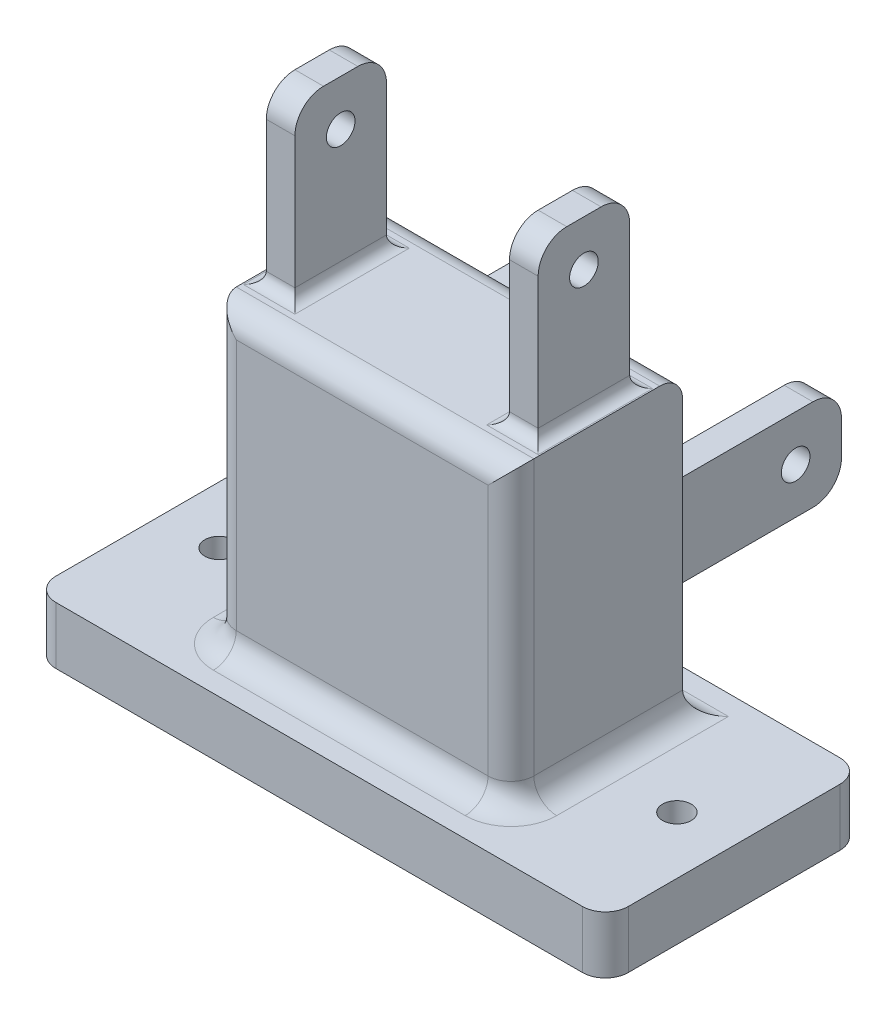
SolidWorks part; units mm, degrees
ref_plane "Front Plane" through (0, 0, 0) normal (0, 0, 1) x (1, 0, 0)
ref_plane "Top Plane" through (0, 0, 0) normal (0, 1, 0) x (1, 0, 0)
ref_plane "Right Plane" through (0, 0, 0) normal (1, 0, 0) x (0, 0, -1)
sketch "Sketch1" plane through (0, 0, 0) normal (0, 1, 0) x (1, 0, 0)
  line L1 (-31.75, -14.2875) -> (31.75, -14.2875)
  line L2 (-31.75, -14.2875) -> (-31.75, 14.2875)
  line L3 (-31.75, 14.2875) -> (31.75, 14.2875)
  line L4 (31.75, -14.2875) -> (31.75, 14.2875)
  line L5 (-31.75, -14.2875) -> (31.75, 14.2875) construction
  line L6 (-31.75, 14.2875) -> (31.75, -14.2875) construction
  point P0 (0, 0)
  dimension "D1" = 63.5
  dimension "D2" = 28.575
extrude "Boss-Extrude1" add sketch "Sketch1" along normal blind 6.35
fillet "Fillet1" radius 2.54 4 edges at (31.75, 3.175, 14.2875) (31.75, 3.175, -14.2875) (-31.75, 3.175, -14.2875) (-31.75, 3.175, 14.2875)
sketch "Sketch2" plane through (0, 6.35, 0) normal (0, 1, 0) x (1, 0, 0)
  line L1 (-16.51, -9.525) -> (16.51, -9.525)
  line L2 (-16.51, -9.525) -> (-16.51, 9.525)
  line L3 (-16.51, 9.525) -> (16.51, 9.525)
  line L4 (16.51, -9.525) -> (16.51, 9.525)
  line L5 (-16.51, -9.525) -> (16.51, 9.525) construction
  line L6 (-16.51, 9.525) -> (16.51, -9.525) construction
  point P0 (0, 0)
  dimension "D1" = 19.05
  dimension "D2" = 33.02
extrude "Boss-Extrude3" add sketch "Sketch2" along normal blind 33.02
shell "Shell1" thickness 6.35
sketch "Sketch3" plane through (0, 0, 0) normal (0, -1, 0) x (1, 0, 0)
  line L0 (-25.4, 0) -> (25.4, 0) construction
  circle A0 centre (-25.4, 0) radius 1.5875
  circle A1 centre (25.4, 0) radius 1.5875
  point P4 (0, 0)
extrude "Cut-Extrude1" cut sketch "Sketch3" against normal blind 6.35
sketch "Sketch4" plane through (0, 39.37, 0) normal (0, 1, 0) x (1, 0, 0)
  line L0 (-15.0812, 0) -> (15.0812, 0) construction
  line L1 (-15.0812, -5.08) -> (-15.0813, 5.08) construction
  line L2 (15.0812, -5.08) -> (15.0812, 5.08) construction
  line L4 (-15.0813, 5.08) -> (-11.9062, 5.08)
  line L5 (-15.0813, 5.08) -> (-15.0812, -5.08)
  line L6 (-15.0812, -5.08) -> (-11.9062, -5.08)
  line L7 (-11.9062, 5.08) -> (-11.9062, -5.08)
  line L8 (15.0812, 5.08) -> (11.9063, 5.08)
  line L9 (15.0812, 5.08) -> (15.0812, -5.08)
  line L10 (15.0812, -5.08) -> (11.9063, -5.08)
  line L11 (11.9063, 5.08) -> (11.9063, -5.08)
  point P4 (0, 0)
  point P8 (-15.0812, 0)
  point P10 (15.0812, 0)
  dimension "D1" = 3.175
  dimension "D2" = 3.175
extrude "Boss-Extrude4" add sketch "Sketch4" along normal blind 19.05
fillet "Fillet4" radius 1.27 8 edges at (-11.9062, 39.37, 0) (-13.4937, 39.37, 5.08) (-13.4938, 39.37, -5.08) (-15.0813, 39.37, 0) (13.4938, 39.37, 5.08) (11.9063, 39.37, 0) (15.0812, 39.37, 0) (13.4938, 39.37, -5.08)
fillet "Fillet6" radius 3.175 4 edges at (-13.4937, 58.42, 5.08) (-13.4938, 58.42, -5.08) (13.4938, 58.42, 5.08) (13.4938, 58.42, -5.08)
sketch "Sketch5" plane through (15.0812, 0, 0) normal (1, 0, 0) x (0, 0, -1)
  line L0 (0, 53.34) -> (0, 58.42) construction
  line L1 (-1.905, 58.42) -> (1.905, 58.42) construction
  circle A0 centre (0, 53.34) radius 1.5875
extrude "Cut-Extrude2" cut sketch "Sketch5" against normal blind 50.8
sketch "Sketch8" plane through (0, 0, -9.525) normal (0, 0, -1) x (-1, 0, 0)
  line L0 (0, 39.37) -> (0, 22.86) construction
  line L1 (-16.51, 39.37) -> (16.51, 39.37) construction
  line L3 (-15.0813, 17.78) -> (15.0812, 17.78) construction
  line L4 (-15.0813, 17.78) -> (-15.0813, 27.94) construction
  line L5 (-15.0813, 27.94) -> (15.0812, 27.94) construction
  line L6 (15.0812, 17.78) -> (15.0812, 27.94) construction
  line L7 (-15.0813, 17.78) -> (15.0812, 27.94) construction
  line L8 (-15.0813, 27.94) -> (15.0812, 17.78) construction
  line L9 (-15.0813, 27.94) -> (-11.9063, 27.94)
  line L10 (-15.0813, 27.94) -> (-15.0813, 17.78)
  line L11 (-15.0813, 17.78) -> (-11.9063, 17.78)
  line L12 (-11.9063, 27.94) -> (-11.9063, 17.78)
  line L13 (15.0812, 27.94) -> (11.9062, 27.94)
  line L14 (15.0812, 27.94) -> (15.0812, 17.78)
  line L15 (15.0812, 17.78) -> (11.9062, 17.78)
  line L16 (11.9062, 27.94) -> (11.9062, 17.78)
  dimension "D1" = 30.1625
  dimension "D2" = 10.16
  dimension "D3" = 3.175
  dimension "D4" = 3.175
extrude "Boss-Extrude5" add sketch "Sketch8" along normal blind 19.05
sketch "Sketch9" plane through (15.0813, 0, 0) normal (1, 0, 0) x (0, 0, -1)
  line L0 (28.575, 22.86) -> (23.495, 22.86) construction
  line L1 (28.575, 17.78) -> (28.575, 27.94) construction
  circle A0 centre (23.495, 22.86) radius 1.5875
extrude "Cut-Extrude3" cut sketch "Sketch9" against normal blind 50.8
fillet "Fillet7" radius 1.27 8 edges at (-11.9062, 22.86, -9.525) (-13.4937, 27.94, -9.525) (-15.0812, 22.86, -9.525) (-13.4937, 17.78, -9.525) (11.9063, 22.86, -9.525) (13.4938, 17.78, -9.525) (13.4938, 27.94, -9.525) (15.0813, 22.86, -9.525)
fillet "Fillet8" radius 2.54 8 edges at (0, 6.35, -9.525) (16.51, 6.35, 0) (-16.51, 6.35, 0) (0, 6.35, 9.525) (-16.51, 22.86, 9.525) (0, 39.37, -9.525) (16.51, 22.86, 9.525) (0, 39.37, 9.525)
fillet "Fillet9" radius 3.175 4 edges at (-13.4937, 17.78, -28.575) (-13.4937, 27.94, -28.575) (13.4938, 17.78, -28.575) (13.4938, 27.94, -28.575)
sketch "Sketch10" plane through (0, 0, 9.525) normal (0, 0, 1) x (1, 0, 0)
  text T0 "<b>  LINE </b>\r\n<b>RIDERS</b>" font "Verdana" height 3.5
